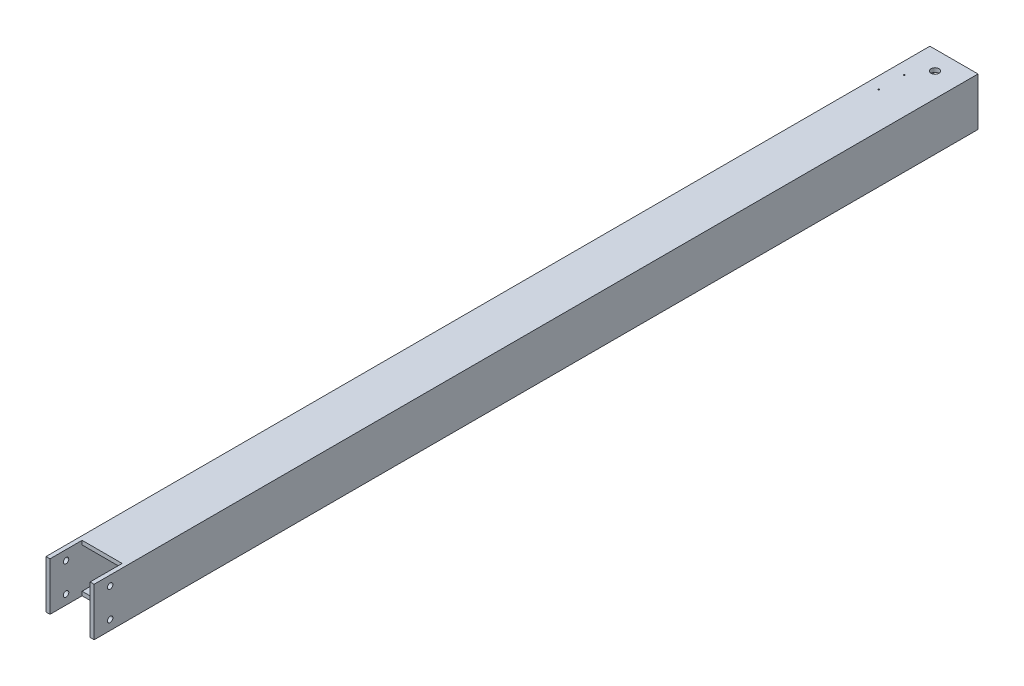
SolidWorks part; units mm, degrees
ref_plane "Plan de face" through (0, 0, 0) normal (0, 0, 1) x (1, 0, 0)
ref_plane "Plan de dessus" through (0, 0, 0) normal (0, 1, 0) x (1, 0, 0)
ref_plane "Plan de droite" through (0, 0, 0) normal (1, 0, 0) x (0, 0, -1)
sketch "Esquisse2" plane through (0, 0, 0) normal (0, 0, 1) x (1, 0, 0)
  line L1 (-19.05, 19.05) -> (19.05, 19.05)
  line L2 (-19.05, 19.05) -> (-19.05, -19.05)
  line L3 (-19.05, -19.05) -> (19.05, -19.05)
  line L4 (19.05, 19.05) -> (19.05, -19.05)
  line L5 (-19.05, 19.05) -> (19.05, -19.05) construction
  line L6 (-19.05, -19.05) -> (19.05, 19.05) construction
  line L7 (-15.875, 15.875) -> (15.875, 15.875)
  line L8 (-15.875, 15.875) -> (-15.875, -15.875)
  line L9 (-15.875, -15.875) -> (15.875, -15.875)
  line L10 (15.875, 15.875) -> (15.875, -15.875)
  line L11 (-15.875, 15.875) -> (15.875, -15.875) construction
  line L12 (-15.875, -15.875) -> (15.875, 15.875) construction
  point P0 (0, 0)
  point P6 (0, 0)
  dimension "D1" = 38.1
  dimension "D2" = 38.1
  dimension "D3" = 3.175
extrude "Boss.-Extru.1" add sketch "Esquisse2" along normal mid plane 700
sketch "Esquisse3" plane through (-19.05, 0, 0) normal (-1, 0, 0) x (0, 0, 1)
  line L0 (350, -19.05) -> (-350, -19.05) construction
  line L1 (350, 19.05) -> (350, -19.05) construction
  circle A0 centre (337.3, -11.43) radius 2.159
  dimension "D1" = 4.318
  dimension "D2" = 7.62
  dimension "D3" = 12.7
extrude "Enlèv. mat.-Extru.1" cut sketch "Esquisse3" against normal through all
mirror "Symétrie1" about plane through (0, 0, 0) normal (0, 1, 0) of "Enlèv. mat.-Extru.1"
sketch "Esquisse4" plane through (0, -19.05, 0) normal (0, -1, 0) x (1, 0, 0)
  line L0 (-19.05, 350) -> (19.05, 350) construction
  line L1 (15.875, 350) -> (-15.875, 350)
  line L2 (15.875, 350) -> (15.875, 324.6)
  line L3 (15.875, 324.6) -> (-15.875, 324.6)
  line L4 (-15.875, 350) -> (-15.875, 324.6)
  line L5 (19.05, 350) -> (19.05, -350) construction
  line L6 (-19.05, 350) -> (-19.05, -350) construction
  dimension "D1" = 3.175
  dimension "D2" = 3.175
  dimension "D3" = 25.4
extrude "Enlèv. mat.-Extru.2" cut sketch "Esquisse4" against normal through all
sketch "Esquisse6" plane through (0, -19.05, 0) normal (0, -1, 0) x (1, 0, 0)
  line L0 (-19.05, -350) -> (19.05, -350) construction
  line L1 (-19.05, 350) -> (-19.05, -350) construction
  circle A0 centre (0, -335) radius 3.175
  dimension "D1" = 6.35
  dimension "D2" = 15
  dimension "D3" = 19.05
extrude "Enlèv. mat.-Extru.3" cut sketch "Esquisse6" against normal through all
sketch "Esquisse7" plane through (19.05, 0, 0) normal (1, 0, 0) x (0, 0, -1)
  line L0 (-337.3, 19.05) -> (-337.3, -19.05) construction
  line L1 (-350, 19.05) -> (350, 19.05) construction
  line L2 (-350, -19.05) -> (350, -19.05) construction
  line L3 (-335.141, 11.43) -> (-339.459, 11.43) construction
  line L4 (-335.141, -11.43) -> (-339.459, -11.43) construction
  circle A0 centre (-337.3, 11.43) radius 2.159 construction
  circle A1 centre (-337.3, -11.43) radius 2.159 construction
  dimension "D1" = 0
sketch "Esquisse8" plane through (0, 0, 0) normal (0, 1, 0) x (1, 0, 0)
  line L0 (9.525, 311.9833) -> (9.525, 50311.9833) construction
  line L1 (-9.525, 306.3762) -> (-9.525, 50306.3762) construction
  line L2 (19.05, -350) -> (19.05, 350) construction
  line L3 (-19.05, -350) -> (-19.05, 350) construction
  line L4 (-19.05, 350) -> (19.05, 350) construction
  circle A0 centre (9.525, 320) radius 0.5
  circle A1 centre (9.525, 300) radius 0.5
  circle A2 centre (-9.525, 300) radius 0.5
  circle A3 centre (-9.525, 320) radius 0.5
  point P16 (0, 0)
  point P17 (0, 0)
  point P18 (9.525, 319.9267)
  point P21 (0, 0)
  dimension "D3" = 1
  dimension "D4" = 20
  dimension "D1" = 9.525
  dimension "D2" = 9.525
  dimension "D5" = 30
extrude "Enlèv. mat.-Extru.4" cut sketch "Esquisse8" against normal through all contours A0 | A1
extrude "Enlèv. mat.-Extru.5" cut sketch "Esquisse8<3>" along normal through all contours A3 | A2
sketch "Esquisse8<3>" plane through (0, 0, 0) normal (0, 1, 0) x (1, 0, 0) same geometry as "Esquisse8"
